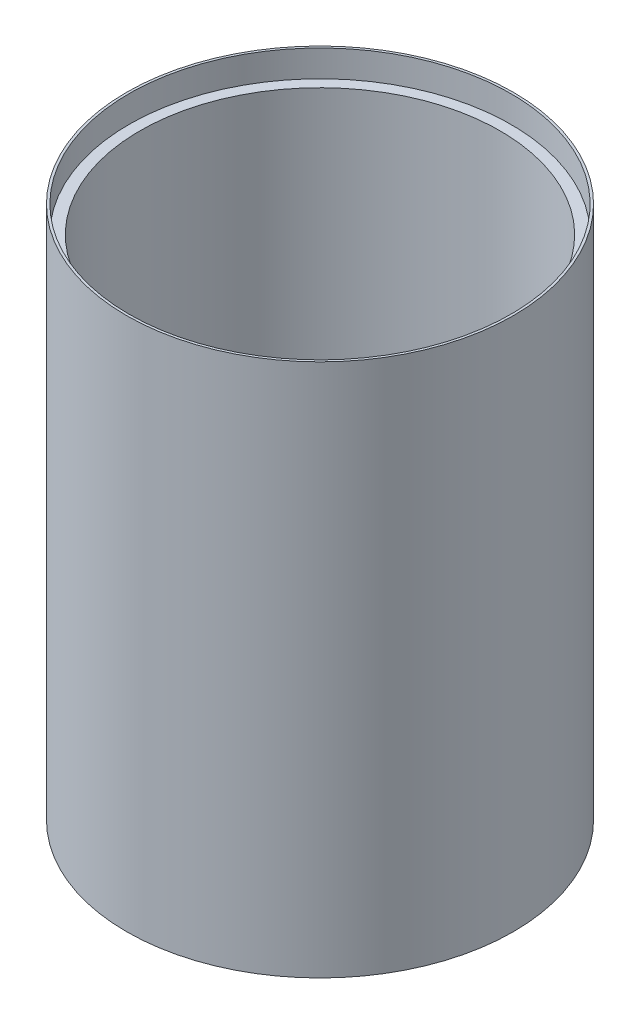
SolidWorks part; units mm, degrees
ref_plane "前基準面" through (0, 0, 0) normal (0, 0, 1) x (1, 0, 0)
ref_plane "上基準面" through (0, 0, 0) normal (0, 1, 0) x (1, 0, 0)
ref_plane "右基準面" through (0, 0, 0) normal (1, 0, 0) x (0, 0, -1)
sketch "草圖6" plane through (0, 0, 0) normal (0, 1, 0) x (1, 0, 0)
  circle A0 centre (0, 0) radius 67.5
  circle A1 centre (0, 0) radius 71.6
  circle A2 centre (0, 0) radius 72.5
  dimension "D1" = 135
  dimension "D2" = 4.1
  dimension "D3" = 145
sketch "草圖7" plane through (0, 0, 0) normal (0, 1, 0) x (1, 0, 0)
  line L1 (-34, 34) -> (34, 34)
  line L2 (-34, 34) -> (-34, -34)
  line L3 (-34, -34) -> (34, -34)
  line L4 (34, 34) -> (34, -34)
  line L5 (-34, 34) -> (34, -34) construction
  line L6 (-34, -34) -> (34, 34) construction
  point P0 (0, 0)
  point P5 (0, 0)
  point P7 (-30, 30)
  point P10 (30, 30)
  point P11 (30, -30)
  point P12 (-30, -30)
  point P13 (0, 0)
  dimension "D1" = 68
  dimension "D2" = 4
  dimension "D3" = 4
extrude "填料-伸長1" add sketch "草圖6" along normal blind 200 contours A2 A1 region at (-72.2949, 0, 0)
extrude "填料-伸長2" add sketch "草圖6<15>" along normal blind 190 contours A1 A0 region at (-69.5748, 0, 0)
sketch "草圖6<15>" plane through (0, 0, 0) normal (0, 1, 0) x (1, 0, 0) same geometry as "草圖6"
extrude "填料-伸長3" add sketch "草圖6<16>" along normal blind 3 contours A0 region at (0, 0, 0)
sketch "草圖6<16>" plane through (0, 0, 0) normal (0, 1, 0) x (1, 0, 0) same geometry as "草圖6"
